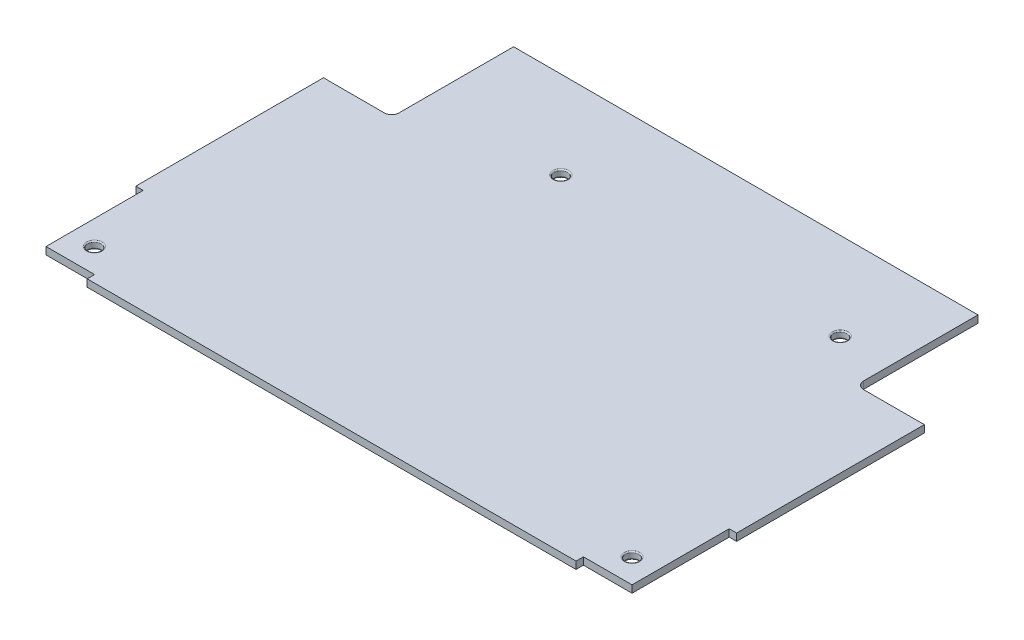
SolidWorks part; units mm, degrees
ref_plane "Front Plane" through (0, 0, 0) normal (0, 0, 1) x (1, 0, 0)
ref_plane "Top Plane" through (0, 0, 0) normal (0, 1, 0) x (1, 0, 0)
ref_plane "Right Plane" through (0, 0, 0) normal (1, 0, 0) x (0, 0, -1)
sketch "Sketch1" plane through (0, 0, 0) normal (0, 1, 0) x (1, 0, 0)
  line L1 (-123.65, -85.2375) -> (123.65, -85.2375)
  line L2 (-123.65, -85.2375) -> (-123.65, 85.2375)
  line L3 (-123.65, 85.2375) -> (123.65, 85.2375)
  line L4 (123.65, -85.2375) -> (123.65, 85.2375)
  line L5 (-123.65, -85.2375) -> (123.65, 85.2375) construction
  line L6 (-123.65, 85.2375) -> (123.65, -85.2375) construction
  point P0 (0, 0)
  dimension "D1" = 247.3
  dimension "D2" = 170.475
extrude "Boss-Extrude1" add sketch "Sketch1" along normal blind 3
sketch "Sketch4" plane through (0, 3, 0) normal (0, 1, 0) x (1, 0, 0)
  line L0 (0, 0) -> (0, -50000) construction
  line L5 (120.6, -82.1875) -> (100.6, -85.2375) construction
  line L15 (-123.65, -85.2375) -> (-120.6, -85.2375)
  line L16 (-123.65, -85.2375) -> (-123.65, -42.1875)
  line L21 (-123.65, -42.1875) -> (-120.6, -42.1875)
  line L23 (-120.6, -82.1875) -> (-120.6, -42.1875)
  line L24 (-123.65, -85.2375) -> (-120.6, -42.1875) construction
  line L25 (-123.65, -42.1875) -> (-120.6, -85.2375) construction
  line L34 (0, 0) -> (50000, 0) construction
  line L35 (-120.6, -85.2375) -> (-100.6, -85.2375)
  line L37 (-120.6, -82.1875) -> (-100.6, -82.1875)
  line L38 (-100.6, -85.2375) -> (-100.6, -82.1875)
  line L39 (-120.6, -85.2375) -> (-100.6, -82.1875) construction
  line L40 (-120.6, -82.1875) -> (-100.6, -85.2375) construction
  line L41 (120.6, -85.2375) -> (100.6, -82.1875) construction
  line L42 (123.65, -42.1875) -> (120.6, -85.2375) construction
  line L43 (123.65, -85.2375) -> (120.6, -42.1875) construction
  line L44 (100.6, -85.2375) -> (100.6, -82.1875)
  line L45 (120.6, -82.1875) -> (100.6, -82.1875)
  line L46 (120.6, -85.2375) -> (100.6, -85.2375)
  line L47 (120.6, -82.1875) -> (120.6, -42.1875)
  line L48 (123.65, -42.1875) -> (120.6, -42.1875)
  line L49 (123.65, -85.2375) -> (123.65, -42.1875)
  line L50 (123.65, -85.2375) -> (120.6, -85.2375)
  point P4 (-122.125, -63.7125)
  point P9 (-110.6, -83.7125)
  point P19 (110.6, -83.7125)
  point P20 (122.125, -63.7125)
  dimension "D1" = 43.05
  dimension "D2" = 3.05
  dimension "D3" = 3.05
  dimension "D4" = 23.05
extrude "Cut-Extrude2" cut sketch "Sketch4" against normal through all
sketch "Sketch2" plane through (0, 3, 0) normal (0, 1, 0) x (1, 0, 0)
  line L0 (0, 0) -> (50000, 0) construction
  line L1 (0, 0) -> (0, 50000) construction
  line L2 (-123.65, 85.2375) -> (-123.65, -42.1875) construction
  line L3 (123.65, 85.2375) -> (-123.65, 85.2375) construction
  line L4 (-100.6, -85.2375) -> (100.6, -85.2375) construction
  circle A0 centre (-110.65, 55.2375) radius 2.75
  circle A1 centre (110.65, 55.2375) radius 2.75
  circle A4 centre (-110.65, -72.2375) radius 2.75
  circle A5 centre (110.65, -72.2375) radius 2.75
  dimension "D1" = 5.5
  dimension "D2" = 13
  dimension "D3" = 30
  dimension "D4" = 13
extrude "Cut-Extrude1" cut sketch "Sketch2" against normal through all
fillet "Fillet1" radius 0.5 8 edges at (-110.65, 3, -52.4875) (-110.65, 0, -52.4875) (110.65, 3, -57.9875) (110.65, 0, -57.9875) (-110.65, 3, 74.9875) (-110.65, 0, 74.9875) (110.65, 3, 69.4875) (110.65, 0, 69.4875)
sketch "Sketch5" plane through (0, 3, 0) normal (0, 1, 0) x (1, 0, 0)
  line L5 (-10, 35.175) -> (10, 35.175)
  line L6 (15.05, 40.225) -> (15.05, 85.2375)
  line L8 (-15.05, 85.2375) -> (-15.05, 40.225)
  line L9 (-10, 35.225) -> (10, 35.225)
  line L10 (15, 40.225) -> (15, 92.225)
  line L11 (15, 92.225) -> (-15, 92.225)
  line L12 (-15, 92.225) -> (-15, 40.225)
  line L13 (-10, 35.225) -> (10, 35.225) construction
  line L14 (15, 40.225) -> (15, 92.225) construction
  line L15 (15, 92.225) -> (-15, 92.225) construction
  line L16 (-15, 92.225) -> (-15, 40.225) construction
  line L17 (15.05, 92.275) -> (-15.05, 92.275) construction
  line L18 (-15.05, 85.2375) -> (15.05, 85.2375)
  line L19 (123.65, 85.2375) -> (-123.65, 85.2375) construction
  line L20 (15.05, 40.225) -> (15.05, 92.275) construction
  line L21 (-15.05, 92.275) -> (-15.05, 40.225) construction
  arc A2 (10, 35.175) -> (15.05, 40.225) centre (10, 40.225) ccw
  arc A3 (-15.05, 40.225) -> (-10, 35.175) centre (-10, 40.225) ccw
  arc A4 (10, 35.225) -> (15, 40.225) centre (10, 40.225) ccw
  arc A5 (-15, 40.225) -> (-10, 35.225) centre (-10, 40.225) ccw
  arc A6 (10, 35.225) -> (15, 40.225) centre (10, 40.225) ccw construction
  arc A7 (-15, 40.225) -> (-10, 35.225) centre (-10, 40.225) ccw construction
  dimension "D1" = 0
  dimension "D2" = 0.05
extrude "Cut-Extrude3" [suppressed] cut sketch "Sketch5" against normal through all
sketch "Sketch6" [suppressed] plane through (0, 3, 0) normal (0, 1, 0) x (1, 0, 0)
  line L0 (-123.65, 105.2375) -> (-123.65, -62.1875) construction
  line L1 (-123.65, -72.4875) -> (-98.57, -72.4875)
  line L2 (-123.65, -72.4875) -> (-123.65, -8.8875)
  line L3 (-123.65, -8.8875) -> (-98.57, -8.8875)
  line L4 (-95.57, -69.4875) -> (-95.57, -11.8875)
  line L5 (-100.6, -105.2375) -> (100.6, -105.2375) construction
  line L6 (0, 0) -> (0, -50000) construction
  line L7 (95.57, -69.4875) -> (95.57, -11.8875)
  line L8 (123.65, -8.8875) -> (98.57, -8.8875)
  line L9 (123.65, -72.4875) -> (123.65, -8.8875)
  line L10 (123.65, -72.4875) -> (98.57, -72.4875)
  arc A0 (98.57, -72.4875) -> (95.57, -69.4875) centre (98.57, -69.4875) cw
  arc A1 (95.57, -11.8875) -> (98.57, -8.8875) centre (98.57, -11.8875) cw
  arc A2 (-98.57, -72.4875) -> (-95.57, -69.4875) centre (-98.57, -69.4875) ccw
  arc A3 (-95.57, -11.8875) -> (-98.57, -8.8875) centre (-98.57, -11.8875) ccw
  point P17 (95.57, -72.4875)
  point P20 (95.57, -8.8875)
  point P23 (-95.57, -72.4875)
  point P26 (-95.57, -8.8875)
  dimension "D4" = 3
  dimension "D1" = 32.75
  dimension "D2" = 63.6
  dimension "D3" = 28.08
extrude "Cut-Extrude4" [suppressed] cut sketch "Sketch6" against normal through all
sketch "Sketch8" [suppressed] plane through (0, 3, 0) normal (0, 1, 0) x (1, 0, 0)
  line L0 (-14.35, -33.2375) -> (-14.35, 49966.7625) construction
  line L1 (53.65, -55.2375) -> (-82.35, -55.2375) construction
  line L2 (53.65, -55.2375) -> (53.65, -11.2375) construction
  line L3 (53.65, -11.2375) -> (-82.35, -11.2375) construction
  line L4 (-82.35, -55.2375) -> (-82.35, -11.2375) construction
  line L5 (53.65, -55.2375) -> (-82.35, -11.2375) construction
  line L6 (53.65, -11.2375) -> (-82.35, -55.2375) construction
  line L7 (-14.35, -33.2375) -> (-50014.35, -33.2375) construction
  circle A0 centre (19.65, -55.2375) radius 1
  circle A1 centre (-14.35, -55.2375) radius 1
  circle A2 centre (-48.35, -55.2375) radius 1
  circle A3 centre (-48.35, -11.2375) radius 1
  circle A4 centre (-14.35, -11.2375) radius 1
  circle A5 centre (19.65, -11.2375) radius 1
  point P4 (-14.35, -33.2375)
  dimension "D1" = 2
  dimension "D3" = 34
extrude "Cut-Extrude6" [suppressed] cut sketch "Sketch8" against normal through all
fillet "Fillet2" [suppressed] radius 0.5
sketch "Sketch9" [suppressed] plane through (0, 3, 0) normal (0, 1, 0) x (1, 0, 0)
  circle A0 centre (-52.194, 74.8945) radius 1.35 construction
  circle A1 centre (5.806, 74.8945) radius 1.35 construction
  circle A2 centre (-74.85, 26.2625) radius 2.75 construction
  circle A3 centre (-52.194, 25.8945) radius 1.35 construction
  circle A4 centre (5.806, 25.8945) radius 1.35 construction
  circle A5 centre (40.15, 26.2625) radius 2.75 construction
  circle A6 centre (-52.194, 74.8945) radius 1.35
  circle A7 centre (5.806, 74.8945) radius 1.35
  circle A8 centre (-74.85, 26.2625) radius 2.75
  circle A9 centre (-52.194, 25.8945) radius 1.35
  circle A10 centre (5.806, 25.8945) radius 1.35
  circle A11 centre (40.15, 26.2625) radius 2.75
extrude "Cut-Extrude7" [suppressed] cut sketch "Sketch9" against normal through all
fillet "Fillet3" [suppressed] radius 0.5
sketch "Sketch10" plane through (0, 3, 0) normal (0, 1, 0) x (1, 0, 0)
  circle A0 centre (74.85, 49.2625) radius 2.75 construction
  circle A1 centre (-40.15, 49.2625) radius 2.75 construction
  circle A2 centre (74.85, 49.2625) radius 2.75
  circle A3 centre (-40.15, 49.2625) radius 2.75
extrude "Cut-Extrude8" cut sketch "Sketch10" against normal through all
fillet "Fillet4" radius 0.5 4 edges at (-40.15, 3, -46.5125) (-40.15, 0, -46.5125) (74.85, 3, -46.5125) (74.85, 0, -46.5125)
sketch "Sketch11" [suppressed] plane through (0, 3, 0) normal (0, 1, 0) x (1, 0, 0)
  line L0 (-100.6, -43.775) -> (100.6, -43.775) construction
  line L1 (-123.65, 43.775) -> (-123.65, -0.725) construction
  circle A0 centre (-83.65, -30.775) radius 2.75
  circle A1 centre (-34.9579, -30.775) radius 2.75
  circle A2 centre (-34.9579, 12.0753) radius 2.75
  circle A3 centre (-83.65, 12.0753) radius 2.75
  dimension "D3" = 5.5
  dimension "D1" = 13
  dimension "D2" = 40
extrude "Cut-Extrude9" [suppressed] cut sketch "Sketch11" against normal through all
fillet "Fillet5" [suppressed] radius 0.5
sketch "Sketch12" [suppressed] plane through (0, 0, 0) normal (0, -1, 0) x (1, 0, 0)
  line L0 (0, 0) -> (0, 50000) construction
  line L4 (98.625, -155.4145) -> (122.675, -155.4145)
  line L5 (125.675, -152.4145) -> (125.675, -94.9145)
  line L6 (122.675, -91.9145) -> (98.625, -91.9145)
  line L7 (95.625, -94.9145) -> (95.625, -152.4145)
  line L9 (125.675, -105.2375) -> (125.675, -94.9145) construction
  line L10 (122.675, -91.9145) -> (98.625, -91.9145) construction
  line L11 (95.625, -94.9145) -> (95.625, -105.2375) construction
  line L12 (123.65, -105.2375) -> (-123.65, -105.2375) construction
  line L13 (123.65, -105.2375) -> (-123.65, -105.2375) construction
  line L15 (125.725, -105.2375) -> (125.725, -94.9145)
  line L16 (122.675, -91.8645) -> (98.625, -91.8645)
  line L17 (95.575, -94.9145) -> (95.575, -105.2375)
  line L18 (95.625, -105.2375) -> (125.675, -105.2375) construction
  line L19 (95.575, -105.2875) -> (125.725, -105.2875) construction
  line L20 (95.575, -105.2375) -> (125.725, -105.2375)
  line L21 (125.725, -105.2875) -> (125.725, -94.9145) construction
  line L22 (95.575, -94.9145) -> (95.575, -105.2875) construction
  line L23 (95.625, -152.4145) -> (95.625, -94.9145) construction
  line L24 (-95.625, -94.9145) -> (-95.625, -105.2375) construction
  line L25 (-122.675, -91.9145) -> (-98.625, -91.9145) construction
  line L26 (-125.675, -105.2375) -> (-125.675, -94.9145) construction
  line L27 (-95.575, -105.2375) -> (-125.725, -105.2375)
  line L28 (-95.575, -94.9145) -> (-95.575, -105.2375)
  line L29 (-122.675, -91.8645) -> (-98.625, -91.8645)
  line L30 (-125.725, -105.2375) -> (-125.725, -94.9145)
  arc A0 (125.725, -94.9145) -> (122.675, -91.8645) centre (122.675, -94.9145) ccw
  arc A1 (98.625, -91.8645) -> (95.575, -94.9145) centre (98.625, -94.9145) ccw
  arc A2 (-98.625, -91.9145) -> (-95.625, -94.9145) centre (-98.625, -94.9145) cw construction
  arc A3 (-125.675, -94.9145) -> (-122.675, -91.9145) centre (-122.675, -94.9145) cw construction
  arc A4 (122.675, -155.4145) -> (125.675, -152.4145) centre (122.675, -152.4145) ccw
  arc A5 (125.675, -94.9145) -> (122.675, -91.9145) centre (122.675, -94.9145) ccw
  arc A6 (98.625, -91.9145) -> (95.625, -94.9145) centre (98.625, -94.9145) ccw
  arc A7 (95.625, -152.4145) -> (98.625, -155.4145) centre (98.625, -152.4145) ccw
  arc A9 (125.675, -94.9145) -> (122.675, -91.9145) centre (122.675, -94.9145) ccw construction
  arc A10 (98.625, -91.9145) -> (95.625, -94.9145) centre (98.625, -94.9145) ccw construction
  arc A12 (-98.625, -91.8645) -> (-95.575, -94.9145) centre (-98.625, -94.9145) cw
  arc A13 (-125.725, -94.9145) -> (-122.675, -91.8645) centre (-122.675, -94.9145) cw
  dimension "D1" = 0
  dimension "D2" = 0.05
extrude "Cut-Extrude10" [suppressed] cut sketch "Sketch12" against normal through all
sketch "Sketch13" plane through (0, 0, 0) normal (0, -1, 0) x (1, 0, 0)
  line L0 (122.675, -35.1105) -> (98.625, -35.1105) construction
  line L1 (95.625, -38.1105) -> (95.625, -95.6105) construction
  line L2 (98.625, -98.6105) -> (122.675, -98.6105) construction
  line L3 (125.675, -95.6105) -> (125.675, -38.1105) construction
  line L4 (-98.625, -35.1105) -> (-122.675, -35.1105) construction
  line L5 (-125.675, -38.1105) -> (-125.675, -95.6105) construction
  line L6 (-122.675, -98.6105) -> (-98.625, -98.6105) construction
  line L7 (-95.625, -95.6105) -> (-95.625, -38.1105) construction
  line L8 (122.675, -35.1105) -> (98.625, -35.1105) construction
  line L9 (95.625, -38.1105) -> (95.625, -95.6105) construction
  line L10 (98.625, -98.6105) -> (122.675, -98.6105) construction
  line L11 (125.675, -95.6105) -> (125.675, -38.1105) construction
  line L12 (-98.625, -35.1105) -> (-122.675, -35.1105) construction
  line L13 (-125.675, -38.1105) -> (-125.675, -95.6105) construction
  line L14 (-122.675, -98.6105) -> (-98.625, -98.6105) construction
  line L15 (-95.625, -95.6105) -> (-95.625, -38.1105) construction
  line L16 (122.675, -35.0605) -> (98.625, -35.0605)
  line L17 (95.575, -38.1105) -> (95.575, -95.6105)
  line L18 (98.625, -98.6605) -> (122.675, -98.6605)
  line L19 (125.725, -95.6105) -> (125.725, -38.1105)
  line L20 (-98.625, -35.0605) -> (-122.675, -35.0605)
  line L21 (-125.725, -38.1105) -> (-125.725, -95.6105)
  line L22 (-122.675, -98.6605) -> (-98.625, -98.6605)
  line L23 (-95.575, -95.6105) -> (-95.575, -38.1105)
  arc A0 (98.625, -35.1105) -> (95.625, -38.1105) centre (98.625, -38.1105) ccw construction
  arc A1 (95.625, -95.6105) -> (98.625, -98.6105) centre (98.625, -95.6105) ccw construction
  arc A2 (122.675, -98.6105) -> (125.675, -95.6105) centre (122.675, -95.6105) ccw construction
  arc A3 (125.675, -38.1105) -> (122.675, -35.1105) centre (122.675, -38.1105) ccw construction
  arc A4 (-122.675, -35.1105) -> (-125.675, -38.1105) centre (-122.675, -38.1105) ccw construction
  arc A5 (-125.675, -95.6105) -> (-122.675, -98.6105) centre (-122.675, -95.6105) ccw construction
  arc A6 (-98.625, -98.6105) -> (-95.625, -95.6105) centre (-98.625, -95.6105) ccw construction
  arc A7 (-95.625, -38.1105) -> (-98.625, -35.1105) centre (-98.625, -38.1105) ccw construction
  arc A8 (98.625, -35.1105) -> (95.625, -38.1105) centre (98.625, -38.1105) ccw construction
  arc A9 (95.625, -95.6105) -> (98.625, -98.6105) centre (98.625, -95.6105) ccw construction
  arc A10 (122.675, -98.6105) -> (125.675, -95.6105) centre (122.675, -95.6105) ccw construction
  arc A11 (125.675, -38.1105) -> (122.675, -35.1105) centre (122.675, -38.1105) ccw construction
  arc A12 (-122.675, -35.1105) -> (-125.675, -38.1105) centre (-122.675, -38.1105) ccw construction
  arc A13 (-125.675, -95.6105) -> (-122.675, -98.6105) centre (-122.675, -95.6105) ccw construction
  arc A14 (-98.625, -98.6105) -> (-95.625, -95.6105) centre (-98.625, -95.6105) ccw construction
  arc A15 (-95.625, -38.1105) -> (-98.625, -35.1105) centre (-98.625, -38.1105) ccw construction
  arc A16 (98.625, -35.0605) -> (95.575, -38.1105) centre (98.625, -38.1105) ccw
  arc A17 (95.575, -95.6105) -> (98.625, -98.6605) centre (98.625, -95.6105) ccw
  arc A18 (122.675, -98.6605) -> (125.725, -95.6105) centre (122.675, -95.6105) ccw
  arc A19 (125.725, -38.1105) -> (122.675, -35.0605) centre (122.675, -38.1105) ccw
  arc A20 (-122.675, -35.0605) -> (-125.725, -38.1105) centre (-122.675, -38.1105) ccw
  arc A21 (-125.725, -95.6105) -> (-122.675, -98.6605) centre (-122.675, -95.6105) ccw
  arc A22 (-98.625, -98.6605) -> (-95.575, -95.6105) centre (-98.625, -95.6105) ccw
  arc A23 (-95.575, -38.1105) -> (-98.625, -35.0605) centre (-98.625, -38.1105) ccw
  dimension "D1" = 0.05
extrude "Cut-Extrude11" cut sketch "Sketch13" against normal through all
